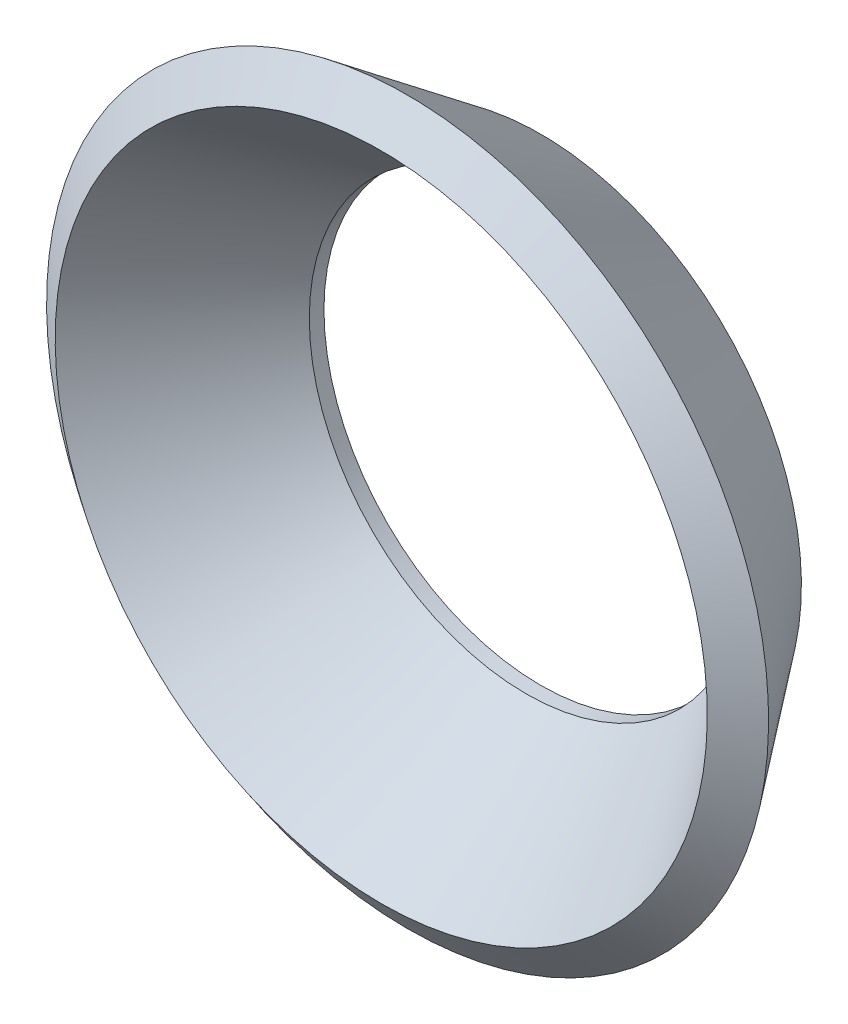
SolidWorks part; units mm, degrees
ref_plane "Front Plane" through (0, 0, 0) normal (0, 0, 1) x (1, 0, 0)
ref_plane "Top Plane" through (0, 0, 0) normal (0, 1, 0) x (1, 0, 0)
ref_plane "Right Plane" through (0, 0, 0) normal (1, 0, 0) x (0, 0, -1)
sketch "Sketch2" plane through (0, 0, 0) normal (1, 0, 0) x (0, 0, -1)
  line L0 (0, 5.2832) -> (0, 0) construction
  line L7 (0, 0) -> (17.2695, 0) construction
  line L14 (0, 5.2832) -> (-3.1735, 5.2832) construction
  line L27 (0, 6.35) -> (-3.2457, 8.7958)
  line L31 (0, 5.2832) -> (0, 6.35)
  line L32 (-0.642, 5.498) -> (-3.8877, 7.9438)
  line L33 (-0.642, 5.498) -> (-0.3569, 5.2832)
  line L34 (-0.3569, 5.2832) -> (0, 5.2832)
  line L35 (-3.2457, 8.7958) -> (-3.8877, 7.9438)
  line L36 (55, 0) -> (-55, 0) construction
  dimension "D1" = 1.0668
  dimension "D6" = 37
  dimension "D2" = 1.0668
  dimension "D3" = 6.35
  dimension "D4" = 4.064
revolve "Revolve1" add sketch "Sketch2" angle 360 about L7
